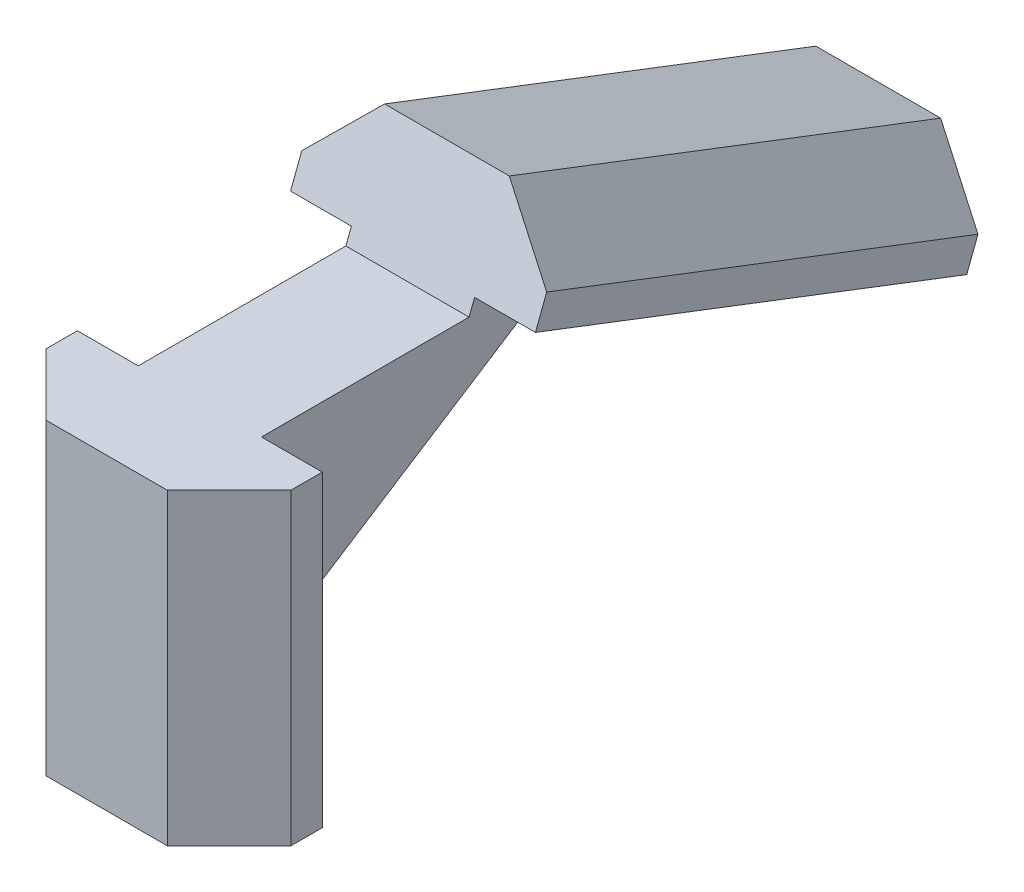
SolidWorks part; units mm, degrees
ref_plane "Front Plane" through (0, 0, 0) normal (0, 0, 1) x (1, 0, 0)
ref_plane "Top Plane" through (0, 0, 0) normal (0, 1, 0) x (1, 0, 0)
ref_plane "Right Plane" through (0, 0, 0) normal (1, 0, 0) x (0, 0, -1)
sketch "Sketch1" plane through (0, 0, 0) normal (0, 1, 0) x (1, 0, 0)
  line L0 (-3.9407, -6.0493) -> (3.9407, -6.0493)
  line L1 (7.95, 0) -> (7.95, -2.04)
  line L2 (7.95, -2.04) -> (3.9407, -6.0493)
  line L4 (0, 0) -> (0, 4.5954) construction
  line L5 (-7.95, -2.04) -> (-3.9407, -6.0493)
  line L6 (-7.95, 0) -> (-7.95, -2.04)
  line L7 (-7.95, 0) -> (7.95, 0)
  dimension "D1" = 15.9
  dimension "D2" = 2.04
  dimension "D3" = 5.67
extrude "Boss-Extrude1" add sketch "Sketch1" against normal blind 20 contours L7 L1 L2 L0 L5 L6
ref_plane "Plane1" through (0, 0, 0) normal (1, 0, 0) x (0, 0, -1)
sketch "Sketch2" plane through (0, 0, 0) normal (1, 0, 0) x (0, 0, -1)
  line L1 (0, -20) -> (0, 0) construction
  line L10 (5.1098, 0) -> (23.7814, -7.1674)
  line L12 (5.1098, 0) -> (6.1849, 2.8007)
  line L13 (6.1849, 2.8007) -> (24.8565, -4.3666)
  line L14 (24.8565, -4.3666) -> (23.7814, -7.1674)
  dimension "D1" = 69
  dimension "D2" = 3
  dimension "D3" = 20
  dimension "D4" = 5.1098
sketch "Sketch4" plane through (0, 0, 0) normal (1, 0, 0) x (0, 0, -1)
  line L0 (0, 0) -> (13.4811, 0)
  line L1 (6.1849, 2.8007) -> (24.8565, -4.3666) construction
  line L2 (13.4811, 0) -> (17.2781, -1.4575)
  line L3 (17.2781, -1.4575) -> (0, -12.5397)
  line L4 (0, -20) -> (0, 0) construction
  line L5 (0, -12.5397) -> (0, 0)
extrude "Boss-Extrude3" add sketch "Sketch4" along normal mid plane 8 contours L5 L0 L2 L3
ref_plane "Plane2" through (0, 5.4439, -2.0897) normal (0, 0.9336, -0.3584) x (1, 0, 0)
sketch "Sketch6" plane through (0, 5.4439, -2.0897) normal (0, 0.9336, -0.3584) x (1, 0, 0)
  line L0 (-4, 16.6528) -> (4, 16.6528)
  line L1 (4, 16.6528) -> (4, 12.5857)
  line L2 (4, 12.5857) -> (-4, 12.5857)
  line L3 (-4, 12.5857) -> (-4, 16.6528)
extrude "Boss-Extrude4" add sketch "Sketch6" against normal up to surface (1 mm away) contours L3 L0 L1 L2 up to face at (0, -0.7288, -15.3796)
ref_plane "Plane3" through (0, -4.5103, -11.7497) normal (0, 0.3584, 0.9336) x (1, 0, 0)
sketch "Sketch8" plane through (0, -4.5103, -11.7497) normal (0, 0.3584, 0.9336) x (1, 0, 0)
  line L0 (-4.05, 11.9869) -> (4.05, 11.9869)
  line L1 (55, 5.8312) -> (-55, 5.8312) construction
  line L2 (7.95, 5.8312) -> (7.95, 7.8712)
  line L3 (7.95, 7.8712) -> (4.05, 11.9869)
  line L4 (-7.95, 5.8312) -> (-7.95, 7.8712)
  line L5 (0, 5.8312) -> (0, 14.4021) construction
  line L6 (-7.95, 7.8712) -> (-4.05, 11.9869)
  line L7 (7.95, 5.8312) -> (-7.95, 5.8312)
  dimension "D1" = 15.9
  dimension "D2" = 5.67
  dimension "D3" = 2.04
  dimension "D4" = 8.1
extrude "Boss-Extrude5" add sketch "Sketch8" against normal blind 30 contours L7 L4 L6 L0 L3 L2
sketch "Sketch9" plane through (4, 0, 0) normal (1, 0, 0) x (0, 0, -1)
  line L0 (17.2781, -1.4575) -> (18.3228, -0.7874)
  line L1 (53.4366, -14.2664) -> (-49.2572, 25.1541) construction
  line L2 (17.2781, -1.4575) -> (0, -12.5397) construction
  line L3 (17.2781, -1.4575) -> (17.6365, -0.524)
  line L4 (17.2781, -1.4575) -> (17.6365, -0.524) construction
  line L5 (17.6365, -0.524) -> (18.3228, -0.7874)
extrude "Boss-Extrude6" add sketch "Sketch9" against normal up to surface (8 mm away) up to face at (-4, -2.2646, -10.3725)
fillet "Fillet1" radius 2 1 edges at (0, -0.7874, -18.3228)
